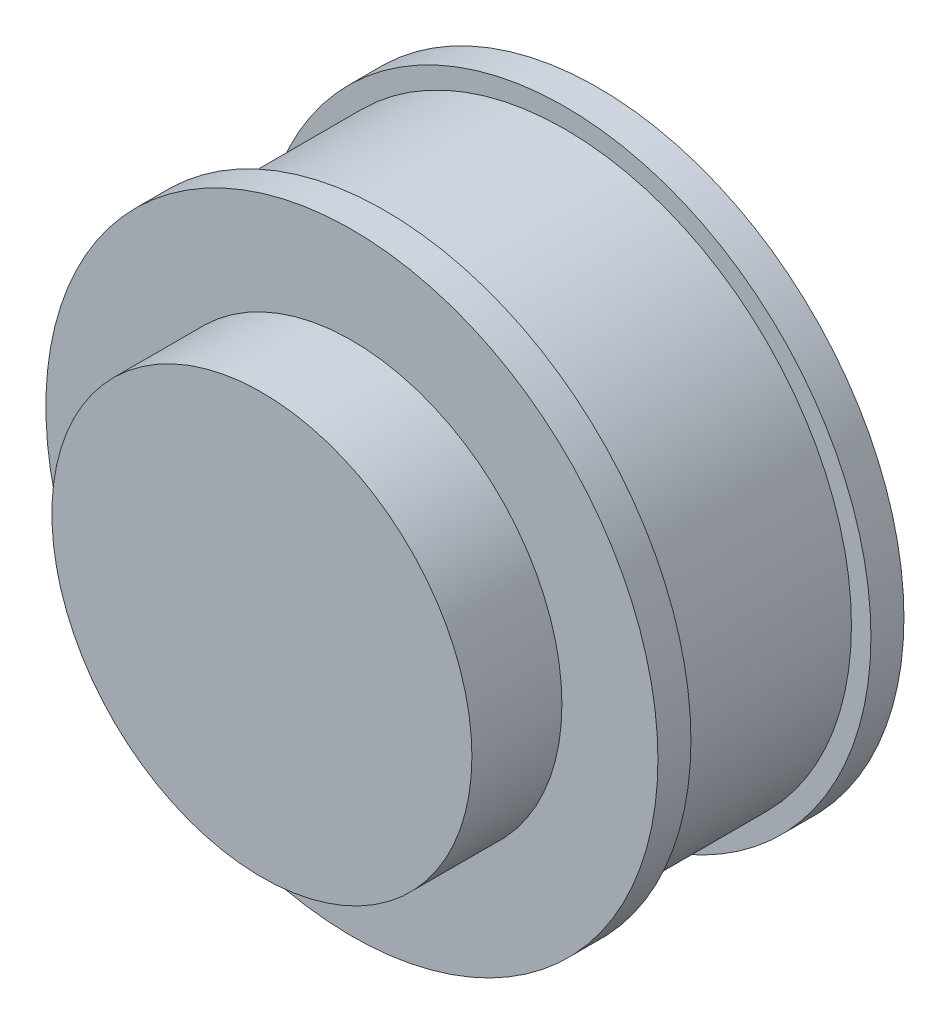
SolidWorks part; units mm, degrees
ref_plane "Płaszczyzna przednia" through (0, 0, 0) normal (0, 0, 1) x (1, 0, 0)
ref_plane "Płaszczyzna górna" through (0, 0, 0) normal (0, 1, 0) x (1, 0, 0)
ref_plane "Płaszczyzna prawa" through (0, 0, 0) normal (1, 0, 0) x (0, 0, -1)
sketch "Szkic1" plane through (0, 0, 0) normal (0, 0, 1) x (1, 0, 0)
  circle A0 centre (0, 0) radius 23.875
  dimension "D1" = 47.75
extrude "Dodanie-wyciągnięcie1" add sketch "Szkic1" along normal blind 20.5
sketch "Szkic2" plane through (0, 0, 20.5) normal (0, 0, 1) x (1, 0, 0)
  circle A0 centre (0, 0) radius 17.5
  dimension "D1" = 35
extrude "Dodanie-wyciągnięcie2" add sketch "Szkic2" along normal blind 7.5
sketch "Szkic3" plane through (0, 0, 20.5) normal (0, 0, 1) x (1, 0, 0)
  circle A0 centre (0, 0) radius 25.5
  dimension "D1" = 51
extrude "Dodanie-wyciągnięcie3" add sketch "Szkic3" against normal blind 2.75
pattern_linear "Szyk liniowy1" count 2 spacing 17.75 along (0, 0, -1) of "Dodanie-wyciągnięcie3"
sketch "Szkic5" [suppressed] plane through (0, 0, 28) normal (0, 0, 1) x (1, 0, 0)
  circle A0 centre (0, 0) radius 5
  dimension "D1" = 10
extrude "Wytnij-wyciągnięcie2" [suppressed] cut sketch "Szkic5" against normal blind 30
sketch "Szkic6" [suppressed] plane through (0, 0, 28) normal (0, 0, 1) x (1, 0, 0)
  line L1 (1.5, 0) -> (-1.5, 0)
  line L2 (1.5, 0) -> (1.5, 7)
  line L3 (1.5, 7) -> (-1.5, 7)
  line L4 (-1.5, 0) -> (-1.5, 7)
  line L5 (1.5, 0) -> (-1.5, 7) construction
  line L6 (1.5, 7) -> (-1.5, 0) construction
  point P0 (0, 3.5)
  dimension "D1" = 7
  dimension "D2" = 3
extrude "Wytnij-wyciągnięcie3" [suppressed] cut sketch "Szkic6" against normal blind 40
